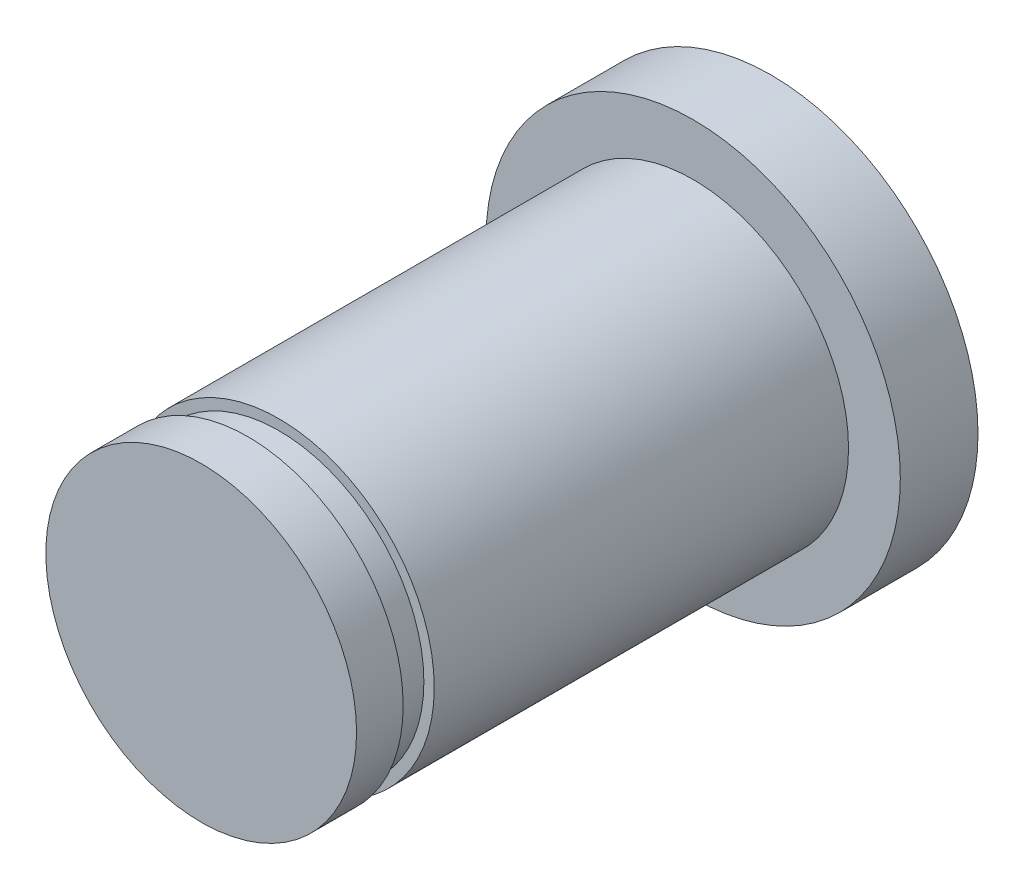
SolidWorks part; units mm, degrees
ref_plane "前视基准面" through (0, 0, 0) normal (0, 0, 1) x (1, 0, 0)
ref_plane "上视基准面" through (0, 0, 0) normal (0, 1, 0) x (1, 0, 0)
ref_plane "右视基准面" through (0, 0, 0) normal (1, 0, 0) x (0, 0, -1)
sketch "草图1" plane through (0, 0, 0) normal (0, 0, 1) x (1, 0, 0)
  circle A0 centre (0.3657, 0.1829) radius 2.8
  circle A1 centre (0.3657, 0.1829) radius 3
  circle A2 centre (0.3657, 0.1829) radius 4
extrude "凸台-拉伸1" add sketch "草图1" along normal blind 1.5 contours A2
extrude "凸台-拉伸2" add sketch "草图1<3>" along normal blind 11 contours A1
sketch "草图1<3>" plane through (0, 0, 0) normal (0, 0, 1) x (1, 0, 0) same geometry as "草图1"
extrude "切除-拉伸1" cut sketch "草图1<4>" against normal blind 0.6 from offset 10.1 flip side to cut contours A0
sketch "草图1<4>" plane through (0, 0, 0) normal (0, 0, 1) x (1, 0, 0) same geometry as "草图1"
